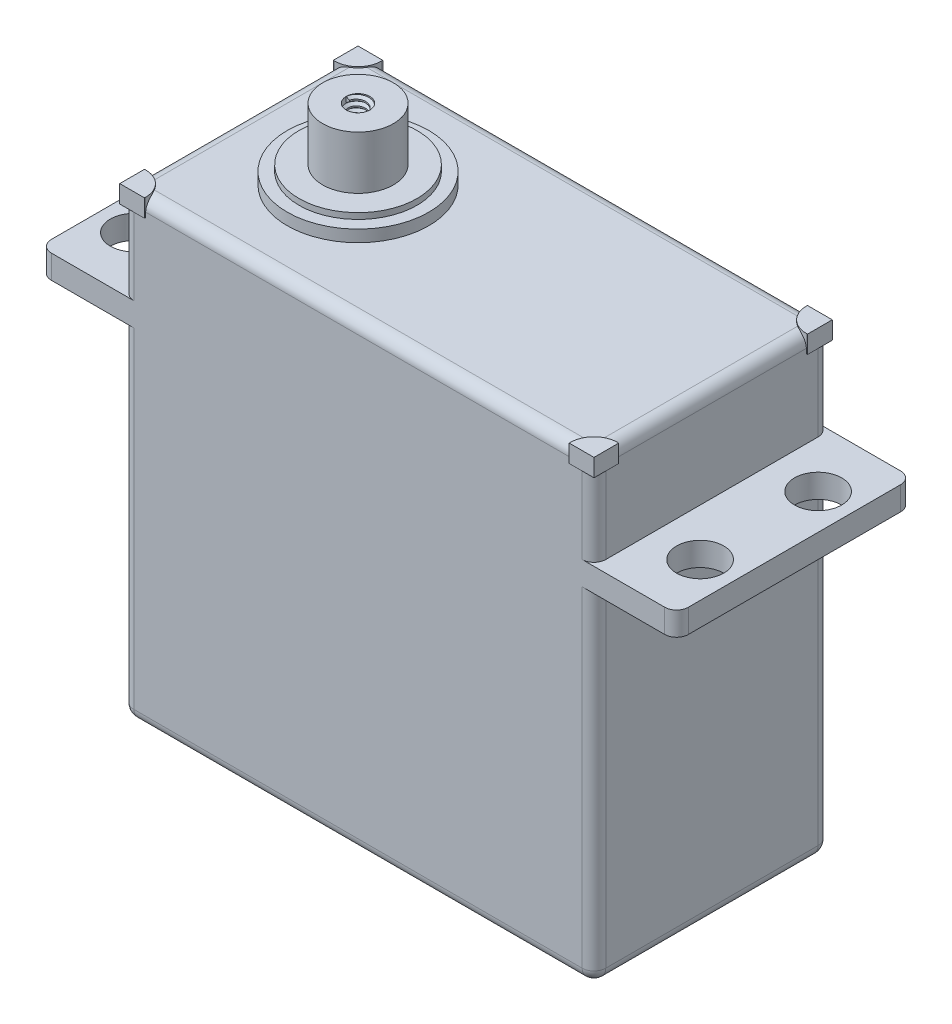
SolidWorks part; units mm, degrees
note: The reader was unsure of these and kept them because the rebuilt part matched: shared geometry of "草图36<4>".
ref_plane "前视基准面" through (0, 0, 0) normal (0, 0, 1) x (1, 0, 0)
ref_plane "上视基准面" through (0, 0, 0) normal (0, 1, 0) x (1, 0, 0)
ref_plane "右视基准面" through (0, 0, 0) normal (1, 0, 0) x (0, 0, -1)
other "Configuration Table"
sketch "草图1" plane through (0, 0, 0) normal (0, 1, 0) x (1, 0, 0)
  line L1 (-20, -10) -> (20, -10)
  line L2 (-20, -10) -> (-20, 10)
  line L3 (-20, 10) -> (20, 10)
  line L4 (20, -10) -> (20, 10)
  line L5 (-20, -10) -> (20, 10) construction
  line L6 (-20, 10) -> (20, -10) construction
  point P0 (0, 0)
  dimension "D1" = 40
  dimension "D2" = 20
extrude "凸台-拉伸1" add sketch "草图1" along normal blind 39
sketch "草图2" plane through (0, 39, 0) normal (0, 1, 0) x (1, 0, 0)
  line L0 (-20, 10) -> (-20, -10) construction
  circle A0 centre (-10, 0) radius 6
  dimension "D2" = 12
  dimension "D1" = 10
extrude "凸台-拉伸2" add sketch "草图2" along normal blind 1
sketch "草图3" plane through (0, 40, 0) normal (0, 1, 0) x (1, 0, 0)
  circle A0 centre (-10, 0) radius 5
  dimension "D1" = 10
extrude "凸台-拉伸3" add sketch "草图3" along normal blind 0.5
sketch "草图4" plane through (0, 40.5, 0) normal (0, 1, 0) x (1, 0, 0)
  circle A0 centre (-10, 0) radius 3
  dimension "D1" = 6
extrude "凸台-拉伸4" add sketch "草图4" along normal blind 4.5
sketch "草图7" plane through (0, 45, 0) normal (0, 1, 0) x (1, 0, 0)
  circle A0 centre (-10, 0) radius 1
  dimension "D1" = 2
extrude "切除-拉伸2" cut sketch "草图7" against normal blind 6
thread "螺纹线1" pitch 0.5 start angle 0, offset 0, length 6, pitch 0.5, diameter 2
ref_plane "基准面5" through (-11, 45, 0) normal (0, 0, 1) x (-1, 0, 0)
sketch "螺纹线轮廓4" plane through (-11, 45, 0) normal (0, 0, 1) x (-1, 0, 0)
  line L0 (0, 0) -> (0, 0.5) construction
  line L11 (0, 0) -> (0, 0.4375)
  line L12 (0, 0.4375) -> (-0.2706, 0.2812)
  line L13 (-0.2706, 0.2812) -> (-0.2706, 0.1562)
  line L15 (-0.2706, 0.1562) -> (0, 0)
  line L17 (-0.2706, 0.2187) -> (0, 0.2187) construction
  point P2 (0, 0)
  dimension "Pitch" = 0.5
  dimension "Profile_Angle" = 60
  dimension "Profile_Land" = 0.125
  dimension "Profile_Height" = 0.2706
sketch "草图35" plane through (-20, 0, 0) normal (-1, 0, 0) x (0, 0, 1)
  line L0 (-10, 31) -> (10, 31)
  line L1 (-10, 31) -> (-10, 29)
  line L2 (10, 31) -> (10, 29)
  line L3 (-10, 29) -> (10, 29)
  line L4 (-10, 39) -> (-10, 0) construction
  line L5 (10, 39) -> (10, 0) construction
  line L6 (-10, 39) -> (10, 39) construction
  dimension "D1" = 8
  dimension "D2" = 2
extrude "凸台-拉伸5" add sketch "草图35" along normal blind 7
sketch "草图36" plane through (0, 31, 0) normal (0, 1, 0) x (1, 0, 0)
  line L0 (-27, 10) -> (-20, 10) construction
  line L1 (-27, -10) -> (-27, 10) construction
  line L2 (-27, -10) -> (-20, -10) construction
  circle A0 centre (-24, 5) radius 2
  circle A1 centre (-24, -5) radius 2
  dimension "D1" = 4
  dimension "D4" = 4
  dimension "D2" = 5
  dimension "D3" = 3
  dimension "D5" = 5
fillet "圆角2" radius 1 2 edges at (-27, 30, -10) (-27, 30, 10)
mirror "镜向1" about plane through (0, 0, 0) normal (1, 0, 0) of "圆角2", "凸台-拉伸5"
extrude "切除-拉伸3" cut sketch "草图36" against normal blind 7 contours A0
extrude "切除-拉伸4" cut sketch "草图36<4>" against normal blind 7 contours A1
sketch "草图36<4>" plane through (0, 31, 0) normal (0, 1, 0) x (1, 0, 0) same geometry as "草图36"
mirror "镜向2" about plane through (0, 0, 0) normal (1, 0, 0) of "切除-拉伸4", "切除-拉伸3"
sketch "草图39" plane through (0, 39, 0) normal (0, 1, 0) x (1, 0, 0)
  line L0 (-20, -10) -> (20, -10) construction
  line L1 (20, -10) -> (20, 10) construction
  line L2 (20, -8) -> (20, -10)
  line L3 (20, -10) -> (18, -10)
  arc A0 (18, -10) -> (20, -8) centre (20, -10) cw
extrude "凸台-拉伸6" add sketch "草图39" along normal blind 0.1
sketch "草图40" plane through (0, 0, 10) normal (0, 0, 1) x (1, 0, 0)
  line L0 (20, 39.1) -> (20, 37.6)
  line L1 (20, 39.1) -> (18, 39.1)
  line L2 (20, 37.6) -> (18, 37.6)
  line L3 (18, 39.1) -> (18, 37.6)
  line L4 (20, 39.1) -> (20, 31) construction
  dimension "D1" = 2
  dimension "D2" = 1.5
extrude "凸台-拉伸7" add sketch "草图40" along normal blind 0.1
sketch "草图41" plane through (20, 0, 0) normal (1, 0, 0) x (0, 0, -1)
  line L0 (-10.1, 39.1) -> (-8, 39.1)
  line L1 (-10.1, 39.1) -> (-10.1, 37.6)
  line L2 (-8, 39.1) -> (-8, 37.6)
  line L3 (-10.1, 37.6) -> (-8, 37.6)
  dimension "D1" = 1.5
extrude "凸台-拉伸8" add sketch "草图41" along normal blind 0.1
mirror "镜向3" about plane through (0, 0, 0) normal (1, 0, 0) of "凸台-拉伸8", "凸台-拉伸7", "凸台-拉伸6" second plane through (0, 0, 0) second plane normal (0, 0, 1)
fillet "圆角5" radius 1 16 edges at (20, 39, 0) (20, 34.3, 10) (0, 39, -10) (0, 39, 10) (-20, 39, 0) (20, 34.3, -10) (-20, 34.3, 10) (-20, 34.3, -10) (-20, 14.5, 10) (0, 0, 10) (-20, 14.5, -10) (-20, 0, 0) (0, 0, -10) (20, 0, 0) (20, 14.5, -10) (20, 14.5, 10)
